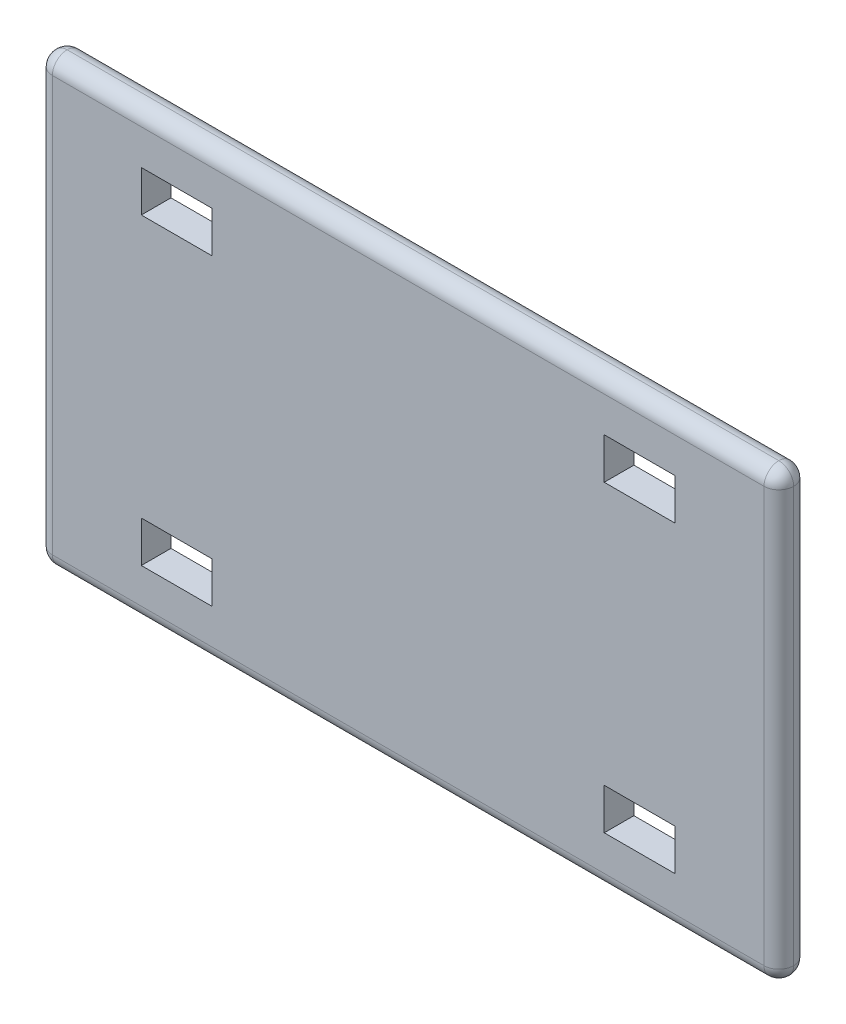
SolidWorks part; units mm, degrees
ref_plane "前视基准面" through (0, 0, 0) normal (0, 0, 1) x (1, 0, 0)
ref_plane "上视基准面" through (0, 0, 0) normal (0, 1, 0) x (1, 0, 0)
ref_plane "右视基准面" through (0, 0, 0) normal (1, 0, 0) x (0, 0, -1)
sketch "草图1" plane through (0, 0, 0) normal (0, 0, 1) x (1, 0, 0)
  line L1 (-9.033, 4.5055) -> (10.967, 4.5055)
  line L2 (-9.033, 4.5055) -> (-9.033, -7.4945)
  line L3 (-9.033, -7.4945) -> (10.967, -7.4945)
  line L4 (10.967, 4.5055) -> (10.967, -7.4945)
extrude "凸台-拉伸1" add sketch "草图1" along normal blind 0.8
fillet "圆角2" radius 0.4 12 edges at (-9.033, 4.5055, 0.4) (-9.033, -1.4945, 0) (-9.033, -7.4945, 0.4) (10.967, -7.4945, 0.4) (0.967, -7.4945, 0) (0.967, 4.5055, 0.8) (10.967, -1.4945, 0.8) (0.967, -7.4945, 0.8) (-9.033, -1.4945, 0.8) (10.967, 4.5055, 0.4) (10.967, -1.4945, 0) (0.967, 4.5055, 0)
sketch "草图2" plane through (0, 0, 0) normal (0, 0, -1) x (-1, 0, 0)
  line L0 (-6.257, 3.1555) -> (-8.167, 3.1555)
  line L4 (-8.167, -6.1445) -> (-8.167, -5.0345)
  line L5 (-8.167, -5.0345) -> (-6.257, -5.0345)
  line L6 (-6.257, -5.0345) -> (-6.257, -6.1445)
  line L7 (-8.167, 3.1555) -> (-8.167, 2.0455)
  line L8 (6.233, 3.1555) -> (4.323, 3.1555)
  line L9 (6.233, -6.1445) -> (4.323, -6.1445)
  line L10 (-6.257, -6.1445) -> (-8.167, -6.1445)
  line L11 (-8.167, 2.0455) -> (-6.257, 2.0455)
  line L12 (-6.257, 2.0455) -> (-6.257, 3.1555)
  line L13 (4.323, -6.1445) -> (4.323, -5.0345)
  line L14 (4.323, -5.0345) -> (6.233, -5.0345)
  line L15 (6.233, -5.0345) -> (6.233, -6.1445)
  line L16 (6.233, 3.1555) -> (6.233, 2.0455)
  line L17 (6.233, 2.0455) -> (4.323, 2.0455)
  line L18 (4.323, 2.0455) -> (4.323, 3.1555)
extrude "切除-拉伸1" cut sketch "草图2" against normal through all
